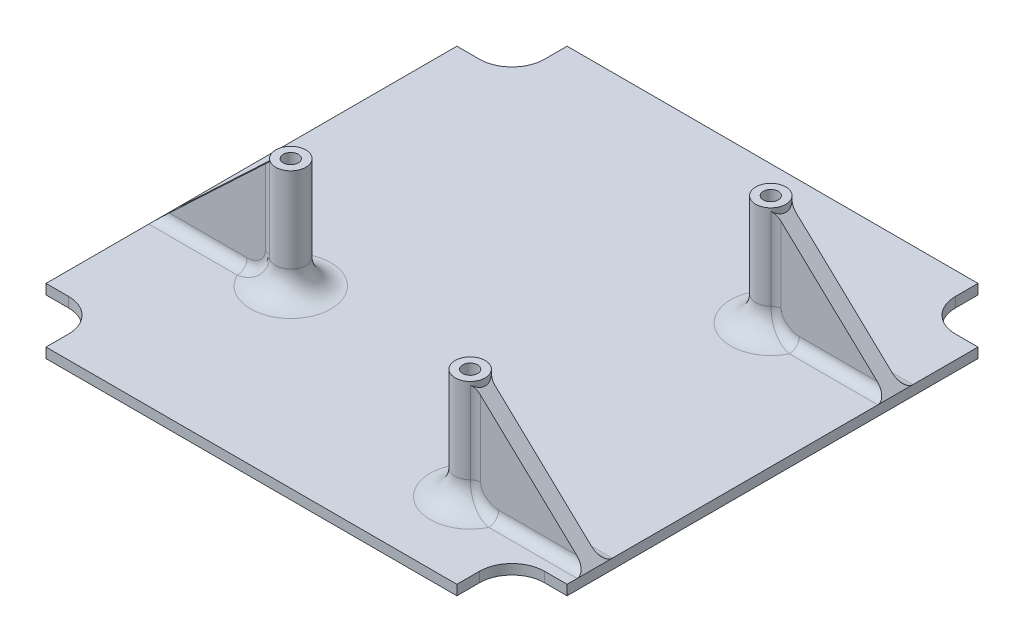
SolidWorks part; units mm, degrees
ref_plane "Front Plane" through (0, 0, 0) normal (0, 0, 1) x (1, 0, 0)
ref_plane "Top Plane" through (0, 0, 0) normal (0, 1, 0) x (1, 0, 0)
ref_plane "Right Plane" through (0, 0, 0) normal (1, 0, 0) x (0, 0, -1)
sketch "Sketch1" plane through (0, 0, 0) normal (0, 1, 0) x (1, 0, 0)
  line L0 (-41.5, 52.5) -> (-41.5, 47.507) construction
  line L1 (-52.5, -52.5) -> (52.5, -52.5) construction
  line L2 (-52.5, -52.5) -> (-52.5, 52.5) construction
  line L3 (-52.5, 52.5) -> (52.5, 52.5) construction
  line L4 (52.5, -52.5) -> (52.5, 52.5) construction
  line L5 (-52.5, -52.5) -> (52.5, 52.5) construction
  line L6 (-52.5, 52.5) -> (52.5, -52.5) construction
  line L7 (41.5, 52.5) -> (41.5, 47.507) construction
  line L8 (0, 52.5) -> (0, -52.5) construction
  line L9 (-52.5, 41.5) -> (-47.507, 41.5) construction
  line L10 (-52.5, -41.5) -> (-47.507, -41.5) construction
  line L11 (-52.5, 0) -> (52.5, 0) construction
  line L12 (-41.5, 52.5) -> (41.5, 52.5) construction
  line L13 (-41.5, -47.507) -> (-41.5, -52.5) construction
  line L14 (47.507, 41.5) -> (52.5, 41.5) construction
  line L15 (52.5, 41.5) -> (52.5, -41.5) construction
  line L16 (47.507, -41.5) -> (52.5, -41.5) construction
  line L17 (41.5, -47.507) -> (41.5, -52.5) construction
  line L18 (41.5, -52.5) -> (-41.5, -52.5) construction
  line L19 (-52.5, -41.5) -> (-52.5, 41.5) construction
  line L20 (-52, -41) -> (-52, 41)
  line L21 (-52, 41) -> (-47.507, 41)
  line L22 (-41, 52) -> (-41, 47.507)
  line L23 (-41, 52) -> (41, 52)
  line L24 (41, 52) -> (41, 47.507)
  line L25 (47.507, 41) -> (52, 41)
  line L26 (52, 41) -> (52, -41)
  line L27 (47.507, -41) -> (52, -41)
  line L28 (41, -47.507) -> (41, -52)
  line L29 (41, -52) -> (-41, -52)
  line L30 (-41, -47.507) -> (-41, -52)
  line L31 (-52, -41) -> (-47.507, -41)
  arc A0 (41.5, 47.507) -> (47.507, 41.5) centre (47.507, 47.507) ccw construction
  arc A2 (47.507, -41.5) -> (41.5, -47.507) centre (47.507, -47.507) ccw construction
  arc A4 (-47.507, 41.5) -> (-41.5, 47.507) centre (-47.507, 47.507) ccw construction
  arc A5 (-47.507, 41) -> (-41, 47.507) centre (-47.507, 47.507) ccw
  arc A6 (41, 47.507) -> (47.507, 41) centre (47.507, 47.507) ccw
  arc A7 (-41.5, -47.507) -> (-47.507, -41.5) centre (-47.507, -47.507) ccw construction
  arc A8 (47.507, -41) -> (41, -47.507) centre (47.507, -47.507) ccw
  arc A9 (-41, -47.507) -> (-47.507, -41) centre (-47.507, -47.507) ccw
  point P0 (0, 0)
  point P21 (35, 35)
  point P25 (-35, 35)
  point P27 (35, -35)
  point P29 (-35, -35)
  dimension "D1" = 105
  dimension "D2" = 70
  dimension "D3" = 83
  dimension "D4" = 0.5
extrude "Boss-Extrude1" add sketch "Sketch1" along normal blind 2
sketch "Sketch2" plane through (0, 0, 0) normal (0, -1, 0) x (1, 0, 0)
  circle A0 centre (35, -35) radius 6
  circle A1 centre (-35, -35) radius 6
  circle A2 centre (-35, 35) radius 6
  circle A3 centre (35, 35) radius 6
  dimension "D1" = 12
sketch "Sketch3" plane through (0, 2, 0) normal (0, 1, 0) x (1, 0, 0)
  line L0 (27.15, 26) -> (27.15, -37) construction
  line L1 (27.15, -37) -> (-27.15, -37) construction
  line L2 (-27.15, -37) -> (-27.15, -15.5) construction
  line L3 (41.5, -52.5) -> (-41.5, -52.5) construction
  circle A0 centre (27.15, 24.5) radius 1.5
  circle A1 centre (27.15, -35.5) radius 1.5
  circle A2 centre (-27.15, -17) radius 1.5
  circle A6 centre (27.15, 24.5) radius 3
  circle A7 centre (27.15, -35.5) radius 3
  circle A8 centre (-27.15, -17) radius 3
  point P4 (-30.15, -17)
  point P6 (0, -37)
  point P21 (24.15, -35.5)
  point P22 (24.15, 24.5)
  dimension "D4" = 3
  dimension "D6" = 17
  dimension "D1" = 63
  dimension "D2" = 54.3
  dimension "D3" = 21.5
  dimension "D5" = 1.5
extrude "Boss-Extrude3" add sketch "Sketch3" along normal blind 22
fillet "Fillet1" radius 5 3 edges at (-27.15, 2, 20) (27.15, 2, 38.5) (27.15, 2, -21.5)
ref_plane "Plane1" through (0, 0, 17) normal (0, 0, 1) x (1, 0, 0)
sketch "Sketch4" plane through (0, 0, 17) normal (0, 0, 1) x (1, 0, 0)
  line L0 (-52, 2) -> (-28.65, 2)
  line L1 (-28.65, 2) -> (-28.65, 24)
  line L2 (-28.65, 24) -> (-52, 2)
  line L3 (-24.15, 24) -> (-30.15, 24) construction
  line L4 (-19.15, 2) -> (-35.15, 2) construction
  line L5 (-24.15, 24) -> (-30.15, 24) construction
extrude "Boss-Extrude4" add sketch "Sketch4" along normal mid plane 3
ref_plane "Plane2" through (0, 0, 35.5) normal (0, 0, 1) x (1, 0, 0)
sketch "Sketch5" plane through (0, 0, 35.5) normal (0, 0, 1) x (1, 0, 0)
  line L0 (28.65, 2) -> (52, 2)
  line L1 (52, 2) -> (28.65, 24)
  line L2 (28.65, 24) -> (28.65, 2)
extrude "Boss-Extrude5" add sketch "Sketch5" along normal mid plane 3
ref_plane "Plane3" through (0, 0, -24.5) normal (0, 0, 1) x (1, 0, 0)
sketch "Sketch6" plane through (0, 0, -24.5) normal (0, 0, 1) x (1, 0, 0)
  line L0 (52, 2) -> (28.65, 24)
  line L1 (28.65, 24) -> (28.65, 2)
  line L2 (28.65, 2) -> (52, 2)
extrude "Boss-Extrude6" add sketch "Sketch6" along normal mid plane 3
fillet "Fillet2" radius 2 18 edges at (-29.7481, 14.9827, 18.5) (-38.559, 10.5637, 18.5) (-29.7481, 14.9827, 15.5) (-38.559, 10.5637, 15.5) (29.7481, 14.9827, 37) (38.8462, 10.259, 37) (29.7481, 14.9827, 34) (38.8462, 10.259, 34) (29.7481, 14.9827, -23) (38.2524, 10.8391, -23) (29.7481, 14.9827, -26) (38.2524, 10.8391, -26) (-43.5041, 2, 18.5) (-43.5041, 2, 15.5) (43.5041, 2, 37) (43.5041, 2, 34) (43.5041, 2, -23) (43.5041, 2, -26)
